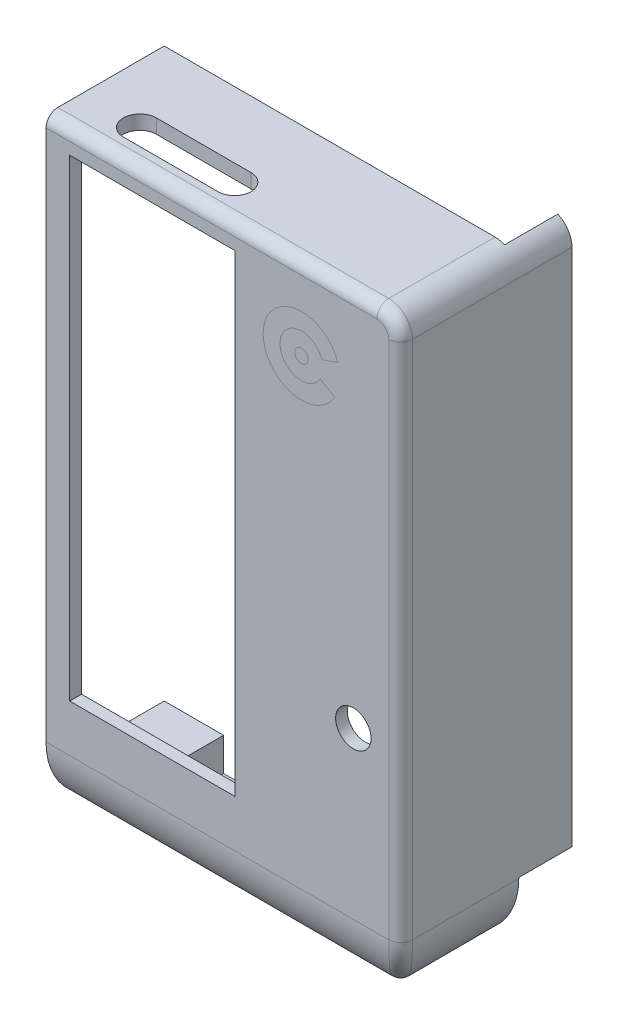
SolidWorks part; units mm, degrees
ref_plane "前视基准面" through (0, 0, 0) normal (0, 0, 1) x (1, 0, 0)
ref_plane "上视基准面" through (0, 0, 0) normal (0, 1, 0) x (1, 0, 0)
ref_plane "右视基准面" through (0, 0, 0) normal (1, 0, 0) x (0, 0, -1)
other "Configuration Table"
sketch "草图1" plane through (0, 0, 0) normal (0, 0, 1) x (1, 0, 0)
  line L1 (-15, 26) -> (15, 26)
  line L2 (-15, 26) -> (-15, -26)
  line L3 (-15, -26) -> (15, -26)
  line L4 (15, 26) -> (15, -26)
  line L5 (-15, 26) -> (15, -26) construction
  line L6 (-15, -26) -> (15, 26) construction
  point P0 (0, 0)
  dimension "D1" = 30
  dimension "D2" = 52
extrude "凸台-拉伸1" add sketch "草图1" against normal blind 10
sketch "草图2" plane through (0, 0, -10) normal (0, 0, -1) x (-1, 0, 0)
  line L0 (15, 26) -> (15, -26) construction
  line L2 (15, -26) -> (-15, -26) construction
  circle A0 centre (12.5, -23.5) radius 0.85
  circle A1 centre (-9.5, -23.5) radius 0.85
  dimension "D1" = 1.7
  dimension "D3" = 2.5
  dimension "D2" = 2.5
  dimension "D4" = 22
  dimension "D5" = 2.5
extrude "切除-拉伸1" cut sketch "草图2" against normal blind 6
sketch "草图3" plane through (0, 0, -10) normal (0, 0, -1) x (-1, 0, 0)
  line L0 (15, 26) -> (15, -26) construction
  line L1 (15, 24.8) -> (-13.8, 24.8)
  line L2 (15, 24.8) -> (15, -22)
  line L3 (15, -22) -> (9.9768, -22)
  line L4 (-13.8, 24.8) -> (-13.8, -22)
  line L5 (-7.8, -22) -> (-13.8, -22)
  line L7 (-7.8, -22) -> (-7.8, -24.8)
  line L8 (-7.8, -24.8) -> (9.9768, -24.8)
  line L9 (9.9768, -22) -> (9.9768, -24.8)
  line L10 (-15, 26) -> (15, 26) construction
  line L11 (-15, -26) -> (-15, 26) construction
  line L12 (15, -26) -> (-15, -26) construction
  dimension "D1" = 1.2
  dimension "D2" = 1.2
  dimension "D3" = 1.2
  dimension "D4" = 5.0232
  dimension "D5" = 2.8
  dimension "D6" = 6
extrude "切除-拉伸2" cut sketch "草图3" against normal blind 9
fillet "圆角1" radius 1 4 edges at (15, 0, 0) (0, 26, 0) (-0.6, 24.8, -1) (13.8, 1.4, -1)
fillet "圆角2" radius 6 4 edges at (15, -26, -5.5) (14.7071, -26, -0.2929) (-1.0884, -24.8, -1) (-0.5, -26, 0)
sketch "草图4" plane through (0, 0, 0) normal (0, 0, 1) x (1, 0, 0)
  line L5 (-13, 24) -> (1, 24)
  line L6 (-13, 24) -> (-13, -16)
  line L7 (-13, -16) -> (1, -16)
  line L8 (1, 24) -> (1, -16)
  line L9 (-15, 25) -> (-15, -20) construction
  line L10 (14, 25) -> (-15, 25) construction
  dimension "D1" = 40
  dimension "D2" = 14
  dimension "D3" = 2
  dimension "D4" = 1
extrude "切除-拉伸3" cut sketch "草图4" against normal through all
sketch "草图5" plane through (0, 0, -10) normal (0, 0, -1) x (-1, 0, 0)
  line L0 (-13.8, 24.8) -> (-13.8, -22) construction
  line L1 (-15, 26) -> (-13.8, 26)
  line L2 (-15, 26) -> (-15, -19.9336)
  line L3 (-15, -19.9336) -> (-13.8, -19.9336)
  line L4 (-13.8, 26) -> (-13.8, -19.9336)
extrude "凸台-拉伸2" add sketch "草图5" along normal blind 4.5
fillet "圆角3" radius 2 4 edges at (13.5071, 24.5071, -1.2929) (14.7071, 25.7071, -0.2929) (15, 26, -7.75) (13.8, 24.8, -6)
sketch "草图7" plane through (0, 0, 0) normal (0, 0, 1) x (1, 0, 0)
  line L2 (-15, -26) -> (9, -26) construction
  line L4 (15, 24) -> (15, -19.9336) construction
  circle A0 centre (11, -6) radius 1.5
  dimension "D1" = 3
  dimension "D2" = 20
  dimension "D3" = 4
extrude "切除-拉伸4" cut sketch "草图7" against normal through all
sketch "草图8" plane through (0, 0, 0) normal (0, 0, 1) x (1, 0, 0)
  line L0 (8.1922, 18.1917) -> (9.4287, 17.4781)
  line L6 (8.338, 19.689) -> (9.6889, 20.1506)
  arc A0 (8.338, 19.689) -> (8.1922, 18.1917) centre (6.6169, 19.1009) ccw
  arc A1 (9.6889, 20.1506) -> (9.4287, 17.4781) centre (6.6169, 19.1009) ccw
extrude "切除-拉伸5" cut sketch "草图8" against normal through all
sketch "草图9" plane through (0, 0, 0) normal (0, 0, 1) x (1, 0, 0)
  line L0 (8.338, 19.689) -> (9.6889, 20.1506) construction
  line L1 (9.4287, 17.4781) -> (8.1922, 18.1917) construction
  line L2 (8.338, 19.689) -> (9.6889, 20.1506)
  line L3 (9.4287, 17.4781) -> (8.1922, 18.1917)
  arc A0 (9.6889, 20.1506) -> (9.4287, 17.4781) centre (6.6169, 19.1009) ccw construction
  arc A1 (9.6889, 20.1506) -> (9.4287, 17.4781) centre (6.6169, 19.1009) ccw
  arc A2 (8.338, 19.689) -> (8.1922, 18.1917) centre (6.6169, 19.1009) ccw construction
  arc A3 (8.338, 19.689) -> (8.1922, 18.1917) centre (6.6169, 19.1009) ccw
extrude "凸台-拉伸3" add sketch "草图9" against normal blind 1 separate body
sketch "草图10" plane through (0, 0, 0) normal (0, 0, 1) x (1, 0, 0)
  circle A0 centre (6.6169, 19.1009) radius 0.5644
extrude "切除-拉伸6" cut sketch "草图10" against normal through all
sketch "草图11" plane through (0, 0, 0) normal (0, 0, 1) x (1, 0, 0)
  circle A0 centre (6.6169, 19.1009) radius 0.5644 construction
  circle A1 centre (6.6169, 19.1009) radius 0.5644
extrude "凸台-拉伸4" add sketch "草图11" against normal blind 1 separate body
sketch "草图12" plane through (0, 26, 0) normal (0, 1, 0) x (1, 0, 0)
  line L0 (-10.0575, 3) -> (-2.0575, 3) construction
  line L1 (-10.0575, 4.4) -> (-2.0575, 4.4)
  line L2 (-10.0575, 1.6) -> (-2.0575, 1.6)
  line L3 (13, 10) -> (-15, 10) construction
  arc A0 (-10.0575, 4.4) -> (-10.0575, 1.6) centre (-10.0575, 3) ccw
  arc A1 (-2.0575, 1.6) -> (-2.0575, 4.4) centre (-2.0575, 3) ccw
  point P2 (-6.0575, 3)
  dimension "D3" = 1.4
  dimension "D1" = 8
  dimension "D2" = 7
extrude "切除-拉伸7" cut sketch "草图12" against normal blind 10
